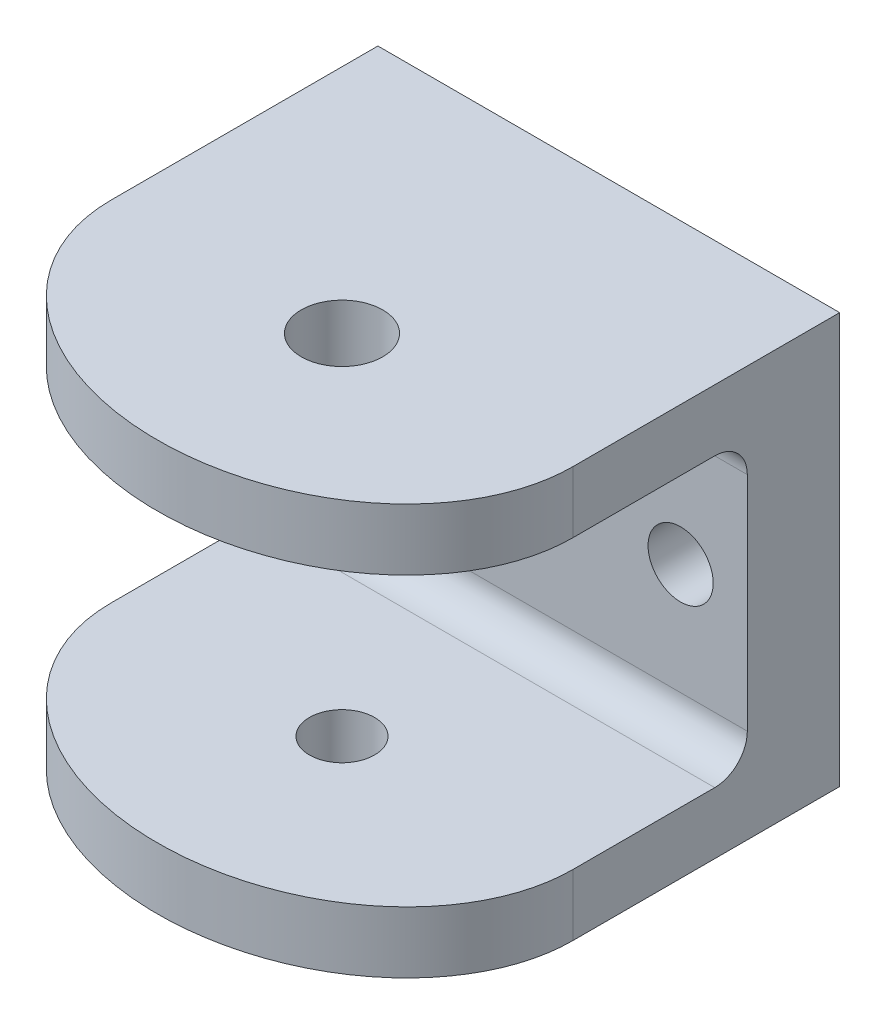
SolidWorks part; units mm, degrees
ref_plane "Front Plane" through (0, 0, 0) normal (0, 0, 1) x (1, 0, 0)
ref_plane "Top Plane" through (0, 0, 0) normal (0, 1, 0) x (1, 0, 0)
ref_plane "Right Plane" through (0, 0, 0) normal (1, 0, 0) x (0, 0, -1)
sketch "Sketch1" plane through (0, 0, 0) normal (0, 0, 1) x (1, 0, 0)
  line L0 (0, 0) -> (-16, 0) construction
  line L1 (-22.5, -20) -> (22.5, -20)
  line L2 (-22.5, -20) -> (-22.5, 20)
  line L3 (-22.5, 20) -> (22.5, 20)
  line L4 (22.5, -20) -> (22.5, 20)
  line L5 (-22.5, -20) -> (22.5, 20) construction
  line L6 (-22.5, 20) -> (22.5, -20) construction
  line L7 (0, 0) -> (16, 0) construction
  circle A0 centre (16, 0) radius 3.175
  circle A1 centre (-16, 0) radius 3.175
  point P0 (0, 0)
  dimension "D4" = 6.35
  dimension "D1" = 45
  dimension "D2" = 40
  dimension "D3" = 32
extrude "Boss-Extrude1" add sketch "Sketch1" along normal blind 9
sketch "Sketch2" plane through (0, 0, 9) normal (0, 0, 1) x (1, 0, 0)
  line L1 (-22.5, 20) -> (22.5, 20)
  line L2 (-22.5, 20) -> (-22.5, 14)
  line L3 (-22.5, 14) -> (22.5, 14)
  line L4 (22.5, -20) -> (22.5, 20)
  line L5 (22.5, 20) -> (-22.5, 20)
  line L6 (-22.5, 20) -> (-22.5, -20)
  line L7 (-22.5, -20) -> (22.5, -20)
  line L8 (22.5, -20) -> (22.5, 20) construction
  line L9 (22.5, 20) -> (-22.5, 20) construction
  line L10 (-22.5, 20) -> (-22.5, -20) construction
  line L11 (-22.5, -20) -> (22.5, -20) construction
  line L12 (22.5, 20) -> (22.5, 14)
  line L13 (22.5, -20) -> (-22.5, -20)
  line L14 (22.5, -20) -> (22.5, -14)
  line L15 (22.5, -14) -> (-22.5, -14)
  line L16 (-22.5, -20) -> (-22.5, -14)
  dimension "D2" = 6
  dimension "D3" = 6
  dimension "D1" = 0
extrude "Boss-Extrude2" add sketch "Sketch2" along normal blind 35
fillet "Fillet1" radius 3.175 2 edges at (0, 14, 9) (0, -14, 9)
sketch "Sketch3" plane through (0, 20, 0) normal (0, 1, 0) x (1, 0, 0)
  line L0 (22.5, -9) -> (-22.5, -9) construction
  line L1 (22.5, -9) -> (-22.5, -9) construction
  line L2 (22.5, -44) -> (22.5, 0) construction
  line L3 (22.5, -44) -> (22.5, -26)
  line L4 (-22.5, -44) -> (-22.5, 0) construction
  line L6 (-22.5, -44) -> (-22.5, -26)
  line L7 (22.5, -44) -> (-22.5, -44)
  line L8 (22.5, 0) -> (-22.5, 0) construction
  circle A0 centre (0, -26) radius 3.175
  ellipse E0 centre (0, -26) end of major axis (-22.5, -26) minor radius 18 (-22.5, -26) -> (7.3951, -9) ccw
  point P4 (0, -9)
  line M6 (-22.5, 0) -> (-22.5, -44)
  line M7 (-22.5, -44) -> (22.5, -44)
  line M8 (22.5, -44) -> (22.5, 0)
  dimension "D1" = 6.35
  dimension "D2" = 26
  dimension "D3" = 22.5
  dimension "D4" = 0
  dimension "D5" = 18
extrude "Cut-Extrude1" cut sketch "Sketch3" against normal through all contours M6 M7 | L7 M8 | A0 region at (17.4767, 20, 39.9774) region at (-17.4742, 20, 39.9794) region at (0, 20, 26)
ref_point "Point4"
ref_point "Point6"
ref_point "Point8"
ref_point "Point12"
sketch "Sketch4" plane through (0, 0, 0) normal (0, 1, 0) x (1, 0, 0)
  point P0 (0, -26)
sketch "Sketch5" plane through (0, 20, 0) normal (0, 1, 0) x (1, 0, 0)
  circle A0 centre (0, -26) radius 3.9688
  dimension "D1" = 7.9375
extrude "Cut-Extrude2" cut sketch "Sketch5" against normal blind 10
